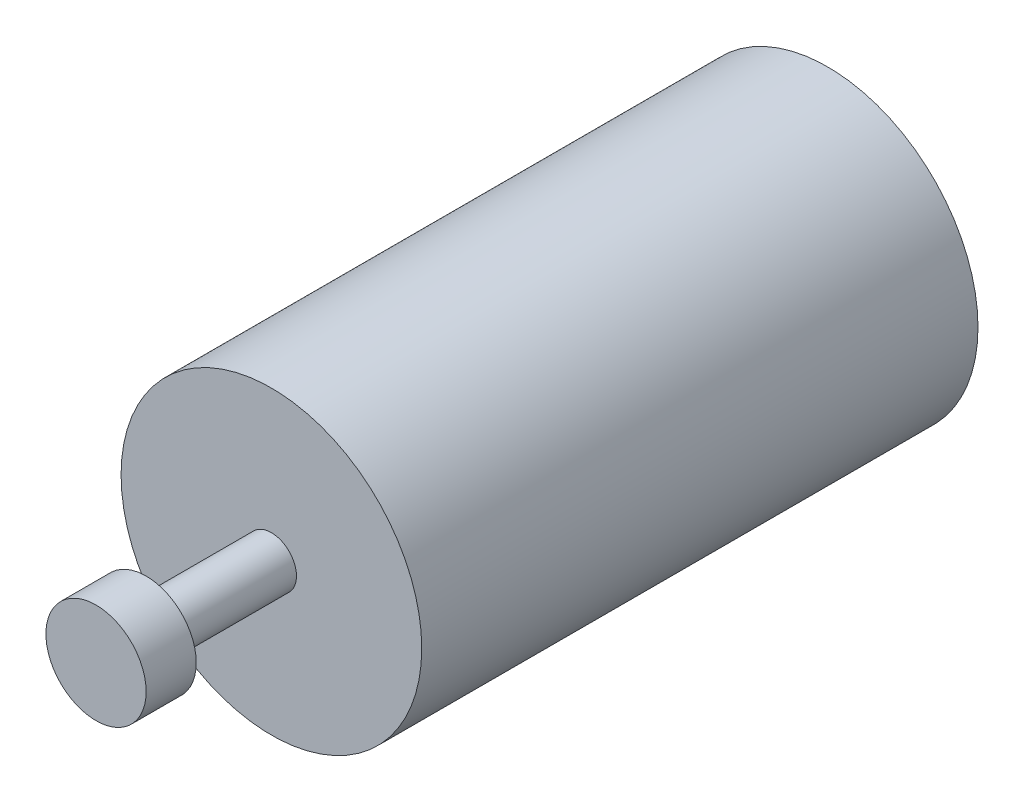
SolidWorks part; units mm, degrees
ref_plane "Front Plane" through (0, 0, 0) normal (0, 0, 1) x (1, 0, 0)
ref_plane "Top Plane" through (0, 0, 0) normal (0, 1, 0) x (1, 0, 0)
ref_plane "Right Plane" through (0, 0, 0) normal (1, 0, 0) x (0, 0, -1)
sketch "Sketch1" plane through (0, 0, 0) normal (0, 0, 1) x (1, 0, 0)
  circle A0 centre (0, 0) radius 6.35
extrude "Boss-Extrude1" add sketch "Sketch1" along normal blind 6.35
sketch "Sketch2" plane through (0, 0, 6.35) normal (0, 0, 1) x (1, 0, 0)
  circle A0 centre (0, 0) radius 38.1
extrude "Boss-Extrude2" add sketch "Sketch2" along normal blind 140.97
sketch "Sketch3" plane through (0, 0, 147.32) normal (0, 0, 1) x (1, 0, 0)
  circle A0 centre (0, 0) radius 6.35
extrude "Boss-Extrude3" add sketch "Sketch3" along normal blind 31.75
sketch "Sketch4" plane through (0, 0, 179.07) normal (0, 0, 1) x (1, 0, 0)
  circle A0 centre (0, 0) radius 12.7
extrude "Boss-Extrude4" add sketch "Sketch4" along normal blind 12.7
